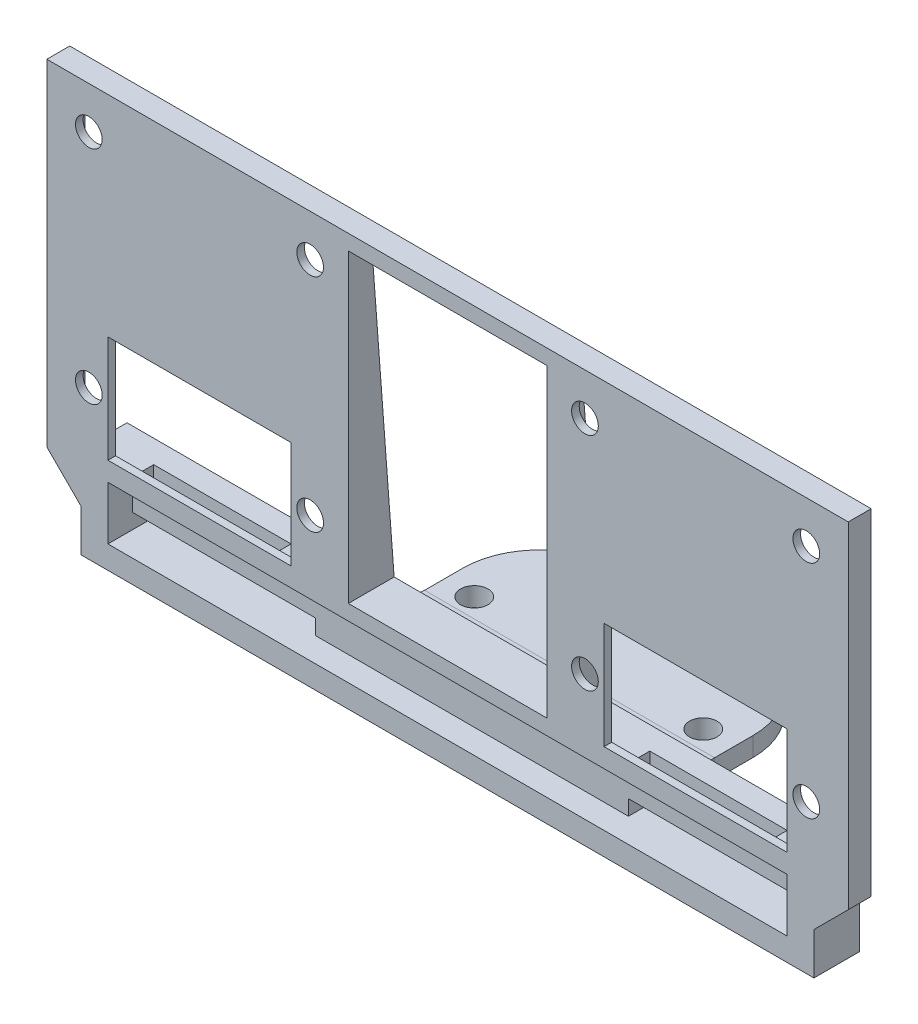
SolidWorks part; units mm, degrees
ref_plane "Front Plane" through (0, 0, 0) normal (0, 0, 1) x (1, 0, 0)
ref_plane "Top Plane" through (0, 0, 0) normal (0, 1, 0) x (1, 0, 0)
ref_plane "Right Plane" through (0, 0, 0) normal (1, 0, 0) x (0, 0, -1)
sketch "Sketch1" plane through (0, 0, 0) normal (0, 0, 1) x (1, 0, 0)
  line L0 (0, -22) -> (0, 22) construction
  line L1 (-52.5, -22) -> (52.5, -22)
  line L2 (-52.5, -22) -> (-52.5, 22)
  line L3 (-52.5, 22) -> (52.5, 22)
  line L4 (52.5, -22) -> (52.5, 22)
  line L5 (-52.5, -22) -> (52.5, 22) construction
  line L6 (-52.5, 22) -> (52.5, -22) construction
  line L7 (0, 0) -> (-32.5, 0) construction
  line L8 (-32.5, 0) -> (-32.5, 13.286) construction
  line L9 (-41.8988, 2) -> (-23.0802, 2) construction
  line L10 (-32.5, 22) -> (-32.5, -22) construction
  line L11 (44.5, -19.5) -> (20.5, -5.5) construction
  line L12 (-44.5, -5.5) -> (-20.5, -5.5)
  line L13 (-44.5, -5.5) -> (-44.5, -19.5)
  line L14 (-44.5, -19.5) -> (-20.5, -19.5)
  line L15 (-20.5, -5.5) -> (-20.5, -19.5)
  line L16 (-44.5, -5.5) -> (-20.5, -19.5) construction
  line L17 (-44.5, -19.5) -> (-20.5, -5.5) construction
  line L18 (44.5, -5.5) -> (20.5, -19.5) construction
  line L19 (41.8988, 2) -> (23.0802, 2) construction
  line L20 (32.5, 0) -> (32.5, 13.286) construction
  line L21 (20.5, -5.5) -> (20.5, -19.5)
  line L22 (44.5, -19.5) -> (20.5, -19.5)
  line L23 (44.5, -5.5) -> (44.5, -19.5)
  line L24 (44.5, -5.5) -> (20.5, -5.5)
  circle A0 centre (-18, 16.5) radius 1.75
  circle A1 centre (-47, 16.5) radius 1.75
  circle A2 centre (-47, -12.5) radius 1.75
  circle A3 centre (-18, -12.5) radius 1.75
  circle A4 centre (18, -12.5) radius 1.75
  circle A5 centre (47, -12.5) radius 1.75
  circle A6 centre (47, 16.5) radius 1.75
  circle A7 centre (18, 16.5) radius 1.75
  point P0 (0, 0)
  point P23 (-32.5, -12.5)
  point P44 (32.5, -12.5)
  dimension "D4" = 3.5
  dimension "D1" = 105
  dimension "D2" = 44
  dimension "D3" = 32.5
  dimension "D5" = 14.5
  dimension "D6" = 14.5
  dimension "D7" = 2
  dimension "D8" = 24
  dimension "D9" = 14
  dimension "D10" = 0
extrude "Boss-Extrude1" add sketch "Sketch1" along normal blind 3
sketch "Sketch2" plane through (0, 0, 0) normal (0, 0, -1) x (-1, 0, 0)
  line L0 (-52.5, 22) -> (52.5, 22) construction
  line L1 (-50.5, -20) -> (-1.5, -20)
  line L2 (-50.5, -20) -> (-50.5, 20)
  line L3 (-50.5, 20) -> (-1.5, 20)
  line L4 (50.5, -20) -> (50.5, 20)
  line L5 (-50.5, -20) -> (50.5, 20) construction
  line L6 (-50.5, 20) -> (50.5, -20) construction
  line L7 (-52.5, -22) -> (-52.5, 22) construction
  line L8 (-1.5, 20) -> (-1.5, -20)
  line L9 (1.5, -20) -> (1.5, 20)
  line L10 (1.5, 20) -> (50.5, 20)
  line L11 (1.5, -20) -> (50.5, -20)
  point P0 (0, 0)
  dimension "D1" = 2
  dimension "D2" = 2
  dimension "D3" = 1.5
  dimension "D4" = 1.5
extrude "Cut-Extrude1" cut sketch "Sketch2" against normal offset from surface (2 mm away) 1 up to face at (-32.5, -12.5, 3)
sketch "Sketch3" plane through (0, -22, 0) normal (0, -1, 0) x (-1, 0, 0)
  line L0 (52.5, 0) -> (-52.5, 0) construction
  line L1 (48, 0) -> (-48, 0)
  line L2 (48, 0) -> (48, 3)
  line L3 (48, 3) -> (-48, 3)
  line L4 (-48, 0) -> (-48, 3)
  line L5 (0, 3) -> (0, 0) construction
  dimension "D1" = 0
  dimension "D2" = 48
  dimension "D3" = 3
extrude "Boss-Extrude2" add sketch "Sketch3" against normal up to surface (2 mm away) up to face at (26, -20, 1)
sketch "Sketch4" plane through (0, -22, 0) normal (0, -1, 0) x (1, 0, 0)
  line L0 (-48, 0) -> (-48, -3) construction
  line L1 (48, -3) -> (-48, -3)
  line L2 (48, -3) -> (48, -0.2)
  line L3 (48, -0.2) -> (-48, -0.2)
  line L4 (-48, -3) -> (-48, -0.2)
  dimension "D1" = 2.8
extrude "Boss-Extrude3" add sketch "Sketch4" along normal blind 10
sketch "Sketch5" plane through (0, 0, 3) normal (0, 0, 1) x (1, 0, 0)
  line L0 (52.5, 22) -> (-52.5, 22) construction
  line L1 (-13, -20) -> (13, -20)
  line L2 (-13, -20) -> (-13, 20)
  line L3 (-13, 20) -> (13, 20)
  line L4 (13, -20) -> (13, 20)
  line L5 (-13, -20) -> (13, 20) construction
  line L6 (-13, 20) -> (13, -20) construction
  circle A0 centre (18, -12.5) radius 1.75 construction
  point P0 (0, 0)
  dimension "D1" = 2
  dimension "D2" = 5
extrude "Cut-Extrude2" cut sketch "Sketch5" against normal through all
sketch "Sketch6" plane through (0, 0, 3) normal (0, 0, 1) x (1, 0, 0)
  line L0 (-32.5, -5.5) -> (-32.5, -0.75) construction
  line L1 (-20.5, -5.5) -> (-44.5, -5.5) construction
  line L2 (0, -20) -> (0, 20) construction
  line L3 (-43.5, 4) -> (-21.5, 4)
  line L4 (-43.5, 4) -> (-43.5, -5.5)
  line L5 (-43.5, -5.5) -> (-21.5, -5.5)
  line L6 (-21.5, 4) -> (-21.5, -5.5)
  line L7 (-43.5, 4) -> (-21.5, -5.5) construction
  line L8 (-43.5, -5.5) -> (-21.5, 4) construction
  line L9 (-13, -20) -> (13, -20) construction
  line L10 (13, 20) -> (-13, 20) construction
  line L11 (43.5, -5.5) -> (21.5, 4) construction
  line L12 (43.5, 4) -> (21.5, -5.5) construction
  line L13 (21.5, 4) -> (21.5, -5.5)
  line L14 (43.5, -5.5) -> (21.5, -5.5)
  line L15 (43.5, 4) -> (21.5, 4)
  line L16 (32.5, -5.5) -> (32.5, -0.75) construction
  line L17 (43.5, 4) -> (43.5, -5.5)
  line L18 (-43.5, -5.5) -> (-21.5, 4) construction
  dimension "D1" = 22
  dimension "D2" = 9.5
  dimension "D3" = 0
extrude "Cut-Extrude5" [suppressed] cut sketch "Sketch6" against normal through all
sketch "Sketch7" plane through (0, 0, 2) normal (0, 0, -1) x (-1, 0, 0)
  line L0 (50.5, 20) -> (-50.5, 20) construction
  line L1 (-13, -20) -> (-14.5, -20)
  line L2 (-13, -20) -> (-13, 20)
  line L3 (-13, 20) -> (-14.5, 20)
  line L4 (-14.5, -20) -> (-14.5, 20)
  line L5 (0, 20) -> (0, -20) construction
  line L6 (-48, -20) -> (48, -20) construction
  line L7 (14.5, -20) -> (14.5, 20)
  line L8 (13, 20) -> (14.5, 20)
  line L9 (13, -20) -> (13, 20)
  line L10 (13, -20) -> (14.5, -20)
  line L11 (-14.5, -20) -> (-14.5, 20)
  line M12 (-13, -20) -> (-13, 20)
  line M13 (-13, 20) -> (-50.5, 20)
  line M15 (-50.5, -20) -> (-13, -20)
  dimension "D1" = 1.5
extrude "Boss-Extrude4" add sketch "Sketch7" along normal up to surface (5 mm away) contours L4 M15 M12 M13 | L9 L10 L7 L8 region at (13.75, 0, 2) region at (-13.75, 0, 2) up to face at (0, -26, -3)
sketch "Sketch8" plane through (14.5, 0, 0) normal (1, 0, 0) x (0, 0, -1)
  line L0 (0, 20) -> (3, -20)
  line L1 (3, -20) -> (3, 20)
  line L2 (3, 20) -> (0, 20)
extrude "Cut-Extrude6" cut sketch "Sketch8" against normal through all
sketch "Sketch9" plane through (0, -22, 0) normal (0, -1, 0) x (1, 0, 0)
  line L0 (0, 3) -> (0, -0.2) construction
  line L1 (-41.5, 2) -> (-23.5, 2)
  line L2 (-41.5, 2) -> (-41.5, 0)
  line L3 (-41.5, 0) -> (-23.5, 0)
  line L4 (-23.5, 2) -> (-23.5, 0)
  line L5 (-41.5, 2) -> (-23.5, 0) construction
  line L6 (-41.5, 0) -> (-23.5, 2) construction
  line L7 (-52.5, 3) -> (52.5, 3) construction
  line L8 (48, -0.2) -> (-48, -0.2) construction
  line L9 (41.5, 0) -> (23.5, 2) construction
  line L10 (41.5, 2) -> (23.5, 0) construction
  line L11 (23.5, 2) -> (23.5, 0)
  line L12 (41.5, 0) -> (23.5, 0)
  line L13 (41.5, 2) -> (41.5, 0)
  line L14 (41.5, 2) -> (23.5, 2)
  point P0 (-32.5, 1)
  point P15 (32.5, 1)
  dimension "D1" = 32.5
  dimension "D2" = 18
  dimension "D3" = 2
  dimension "D4" = 1
extrude "Cut-Extrude7" cut sketch "Sketch9" against normal blind 5
sketch "Sketch10" plane through (0, -32, 0) normal (0, -1, 0) x (1, 0, 0)
  line L0 (0, 0) -> (0, -3) construction
  line L1 (-48, -3) -> (48, -3) construction
  line L2 (0, -28) -> (0, -3) construction
  line L3 (-19, -3) -> (19, -3)
  line L4 (-19, -3) -> (-19, -28)
  line L5 (-19, -28) -> (19, -28)
  line L6 (19, -3) -> (19, -28)
  dimension "D1" = 38
  dimension "D2" = 25
extrude "Boss-Extrude7" add sketch "Sketch10" against normal blind 2.5
sketch "Sketch11" plane through (0, -32, 0) normal (0, -1, 0) x (1, 0, 0)
  line L0 (0, -28) -> (0, 0) construction
  line L1 (-19, -28) -> (19, -28) construction
  line L2 (-19, -15.5) -> (19, -15.5) construction
  line L3 (-19, -3) -> (-19, -28) construction
  line L4 (19, -28) -> (19, -3) construction
  circle A0 centre (15, -15.5) radius 1.8
  circle A1 centre (-15, -15.5) radius 1.8
  circle A2 centre (0, -23.5) radius 1.8
  circle A3 centre (0, -7.5) radius 1.8
  dimension "D1" = 3.6
  dimension "D4" = 3.6
  dimension "D2" = 15
  dimension "D3" = 8
extrude "Cut-Extrude8" cut sketch "Sketch11" against normal through all
fillet "Fillet1" radius 10 5 edges at (19, -30.75, -28) (-19, -30.75, -28) (0, -29.5, -3)
sketch "Sketch12" plane through (0, -32, 0) normal (0, -1, 0) x (1, 0, 0)
  circle A0 centre (0, -7.5) radius 3.5
  dimension "D1" = 7
extrude "Cut-Extrude10" cut sketch "Sketch12" along normal up to surface (-2.5 mm away) from offset 10 up to face at (0, -29.5, -25.3) offset against normal yes
sketch "Sketch13" plane through (0, 0, -0.2) normal (0, 0, 1) x (1, 0, 0)
  line L0 (-48, -27) -> (48, -27) construction
  line L1 (-48, -32) -> (-48, -22) construction
  line L2 (48, -32) -> (48, -22) construction
  line L3 (0, -22) -> (0, -32) construction
  line L4 (-52.5, -22) -> (52.5, -22) construction
  line L5 (48, -32) -> (-48, -32) construction
  line L6 (32.5, -19.5) -> (32.5, -32) construction
  line L7 (20.5, -19.5) -> (44.5, -19.5) construction
  line L8 (-20.5, -29) -> (-44.5, -27) construction
  line L9 (20.5, -27) -> (44.5, -27)
  line L10 (20.5, -27) -> (20.5, -29)
  line L11 (20.5, -29) -> (44.5, -29)
  line L12 (44.5, -27) -> (44.5, -29)
  line L13 (20.5, -27) -> (44.5, -29) construction
  line L14 (20.5, -29) -> (44.5, -27) construction
  line L15 (-20.5, -27) -> (-44.5, -29) construction
  line L16 (-32.5, -19.5) -> (-32.5, -32) construction
  line L17 (-44.5, -27) -> (-44.5, -29)
  line L18 (-20.5, -29) -> (-44.5, -29)
  line L19 (-20.5, -27) -> (-20.5, -29)
  line L20 (-20.5, -27) -> (-44.5, -27)
  point P12 (32.5, -28)
  point P27 (-32.5, -28)
  dimension "D1" = 2
  dimension "D2" = 1
extrude "Cut-Extrude11" cut sketch "Sketch13" against normal through all
sketch "Sketch14" plane through (0, 0, -0.2) normal (0, 0, 1) x (1, 0, 0)
  line L0 (48, -32) -> (-48, -32) construction
  line L1 (-48, -22) -> (-44.5, -22)
  line L2 (-48, -22) -> (-48, -32)
  line L3 (-48, -32) -> (-44.5, -32)
  line L4 (-44.5, -22) -> (-44.5, -32)
  line L5 (-44.5, -27) -> (-44.5, -29) construction
  line L6 (0, 0) -> (0, -10.7923) construction
  line L7 (44.5, -22) -> (44.5, -32)
  line L8 (48, -32) -> (44.5, -32)
  line L9 (48, -22) -> (48, -32)
  line L10 (48, -22) -> (44.5, -22)
extrude "Boss-Extrude8" add sketch "Sketch14" along normal up to surface (3.2 mm away) up to face at (0, 0, 3)
sketch "Sketch15" plane through (0, 0, -0.2) normal (0, 0, 1) x (1, 0, 0)
  line L0 (-44.5, -22) -> (-44.5, -32) construction
  line L1 (-44.5, -29) -> (44.5, -29)
  line L2 (-44.5, -29) -> (-44.5, -32)
  line L3 (-44.5, -32) -> (44.5, -32)
  line L4 (44.5, -29) -> (44.5, -32)
  line L5 (-44.5, -29) -> (-20.5, -29) construction
extrude "Boss-Extrude9" add sketch "Sketch15" along normal up to surface (3.2 mm away)
chamfer "Chamfer1" distance 4.5 angle 45 2 edges
chamfer "Chamfer2" distance 2 angle 45 1 edges
